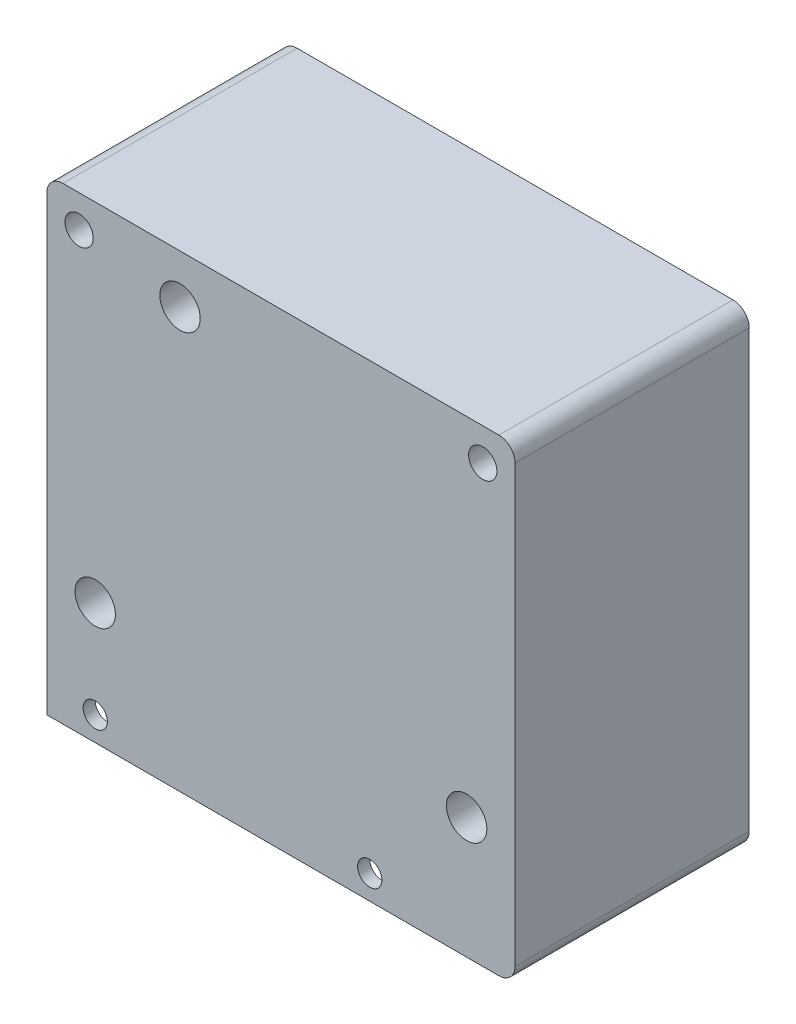
SolidWorks part; units mm, degrees
ref_plane "Front Plane" through (0, 0, 0) normal (0, 0, 1) x (1, 0, 0)
ref_plane "Top Plane" through (0, 0, 0) normal (0, 1, 0) x (1, 0, 0)
ref_plane "Right Plane" through (0, 0, 0) normal (1, 0, 0) x (0, 0, -1)
sketch "Sketch1" plane through (0, 0, 0) normal (0, 0, 1) x (1, 0, 0)
  line L0 (-29, -29) -> (17.5, -29)
  line L1 (17.5, -29) -> (17.5, -23)
  line L2 (17.5, -23) -> (-29, -23)
  line L3 (-29, -23) -> (-29, -29)
  line L4 (29, -27) -> (29, 27)
  line L5 (27, 29) -> (-27, 29)
  line L6 (-29, 27) -> (-29, -23)
  line L7 (-29, -23) -> (17.5, -23)
  line L8 (17.5, -23) -> (17.5, -29)
  line L9 (17.5, -29) -> (27, -29)
  circle A0 centre (-23, -26) radius 1.5
  circle A1 centre (11, -26) radius 1.5
  circle A2 centre (23, -14) radius 2.5
  circle A3 centre (-23, -14) radius 2.5
  circle A4 centre (25, 25) radius 1.75
  circle A5 centre (-12.5, 23) radius 2.5
  circle A6 centre (-25, 25) radius 1.75
  arc A7 (27, -29) -> (29, -27) centre (27, -27) ccw
  arc A8 (29, 27) -> (27, 29) centre (27, 27) ccw
  arc A9 (-27, 29) -> (-29, 27) centre (-27, 27) ccw
  dimension "D1" = 3
  dimension "D2" = 5
  dimension "D3" = 3.5
  dimension "D4" = 2
  dimension "D5" = 11
  dimension "D6" = 17.5
  dimension "D7" = 23
  dimension "D8" = 25
  dimension "D9" = 29
  dimension "D10" = 12.5
  dimension "D11" = 23
  dimension "D12" = 25
  dimension "D13" = 29
  dimension "D14" = 23
  dimension "D15" = 25
  dimension "D16" = 29
  dimension "D17" = 14
  dimension "D18" = 23
  dimension "D19" = 26
extrude "Boss-Extrude1" add sketch "Sketch1" along normal blind 29 contours L5 A9 L6 L2 L1 L9 A7 L4 A8 A2 A3 A4 A5 A6 | L2 L3 L0 L1 A1 A0 region at (-5.7367, -26, 0) region at (0.6075, 2.279, 0)
extrude "Cut-Extrude1" cut sketch "Sketch1<3>" along normal blind 27.5 contours L2 L3 L0 L1 A1 A0 region at (-5.7367, -26, 0)
sketch "Sketch1<3>" plane through (0, 0, 0) normal (0, 0, 1) x (1, 0, 0) same geometry as "Sketch1"
